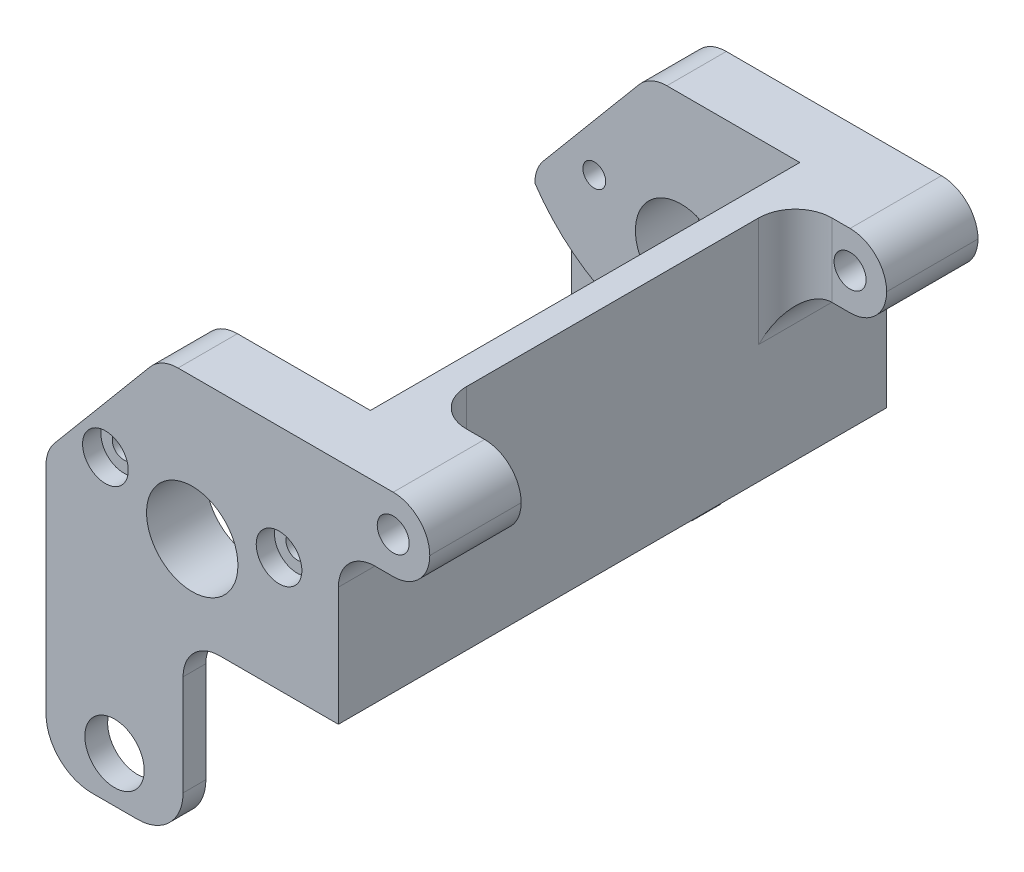
SolidWorks part; units mm, degrees
ref_plane "Front Plane" through (0, 0, 0) normal (0, 0, 1) x (1, 0, 0)
ref_plane "Top Plane" through (0, 0, 0) normal (0, 1, 0) x (1, 0, 0)
ref_plane "Right Plane" through (0, 0, 0) normal (1, 0, 0) x (0, 0, -1)
sketch "Sketch2" plane through (0, 0, 0) normal (0, 0, 1) x (1, 0, 0)
  line L0 (-7.5, 5) -> (-7.5, 30)
  line L1 (-7.5, 30) -> (5.0865, 45)
  line L2 (5.0865, 45) -> (24.5, 45)
  line L3 (24.5, 45) -> (24.5, 20)
  line L4 (24.5, 20) -> (7.5, 20)
  line L5 (7.5, 20) -> (7.5, 5)
  line L6 (-2.5, 0) -> (2.5, 0)
  line L7 (-7.5, 0) -> (7.5, 0) construction
  line L8 (-7.5, 5) -> (7.5, 5) construction
  line L9 (18.0048, 32.5697) -> (-0.9952, 32.5697) construction
  line L10 (8.5048, 32.5697) -> (8.5048, 29.5697) construction
  line L11 (0, 5) -> (8.5048, 29.5697) construction
  circle A5 centre (0, 5) radius 3.25
  circle A6 centre (18.0048, 32.5697) radius 1.25
  circle A7 centre (-0.9952, 32.5697) radius 1.25
  circle A8 centre (8.5048, 29.5697) radius 5
  circle A9 centre (8.5048, 32.5697) radius 12.5 construction
  arc A10 (2.5, 0) -> (7.5, 5) centre (2.5, 5) ccw
  arc A11 (-7.5, 5) -> (-2.5, 0) centre (-2.5, 5) ccw
  dimension "D3" = 6.5
  dimension "D4" = 5
  dimension "D10" = 10
  dimension "D12" = 2.5
  dimension "D14" = 25
  dimension "D15" = 5
  dimension "D1" = 40
  dimension "D2" = 15
  dimension "D5" = 30
  dimension "D6" = 15
  dimension "D7" = 17
  dimension "D8" = 20
  dimension "D9" = 19
  dimension "D11" = 3
  dimension "D13" = 26
extrude "Boss-Extrude1" add sketch "Sketch2" along normal blind 30 and the other way blind 30
sketch "Sketch3" plane through (0, 45, 0) normal (0, 1, 0) x (1, 0, 0)
  line L0 (-7.5, -30) -> (-7.5, 30) construction
  line L1 (-36.5, -27.5) -> (21.5, -27.5)
  line L2 (-36.5, -27.5) -> (-36.5, 27.5)
  line L3 (-36.5, 27.5) -> (21.5, 27.5)
  line L4 (21.5, -27.5) -> (21.5, 27.5)
  line L5 (-36.5, -27.5) -> (21.5, 27.5) construction
  line L6 (-36.5, 27.5) -> (21.5, -27.5) construction
  line L7 (24.5, 30) -> (5.0865, 30) construction
  line L8 (24.5, -30) -> (24.5, 30) construction
  point P0 (-7.5, 0)
  dimension "D1" = 2.5
  dimension "D2" = 3
extrude "Cut-Extrude1" cut sketch "Sketch3" against normal through all
sketch "Sketch4" plane through (24.5, 0, 0) normal (1, 0, 0) x (0, 0, -1)
  line L1 (-30, 45) -> (-20, 45)
  line L2 (-30, 45) -> (-30, 37)
  line L3 (-30, 37) -> (-20, 37)
  line L4 (-20, 45) -> (-20, 37)
  dimension "D1" = 10
  dimension "D2" = 8
extrude "Boss-Extrude2" add sketch "Sketch4" along normal blind 10
fillet "Fillet1" radius 4 2 edges at (34.5, 37, 25) (34.5, 45, 25)
sketch "Sketch5" plane through (0, 0, 20) normal (0, 0, -1) x (-1, 0, 0)
  circle A0 centre (-30.5, 41) radius 1.75
  dimension "D1" = 3.5
extrude "Cut-Extrude2" cut sketch "Sketch5" against normal through all
mirror "Mirror1" about plane through (0, 0, 0) normal (0, 0, 1) of "Cut-Extrude2", "Fillet1", "Boss-Extrude2"
fillet "Fillet2" radius 4 10 edges at (24.5, 41, -20) (24.5, 41, 20) (5.0865, 45, -28.75) (7.5, 20, -28.75) (24.5, 37, -25) (24.5, 37, 25) (7.5, 20, 28.75) (5.0865, 45, 28.75) (-7.5, 30, 28.75) (-7.5, 30, -28.75)
sketch "Sketch6" plane through (0, 0, -27.5) normal (0, 0, 1) x (1, 0, 0)
  line L0 (-0.9952, 32.5697) -> (18.0048, 32.5697) construction
  line L7 (21.5, 45) -> (6.9517, 45)
  line L8 (3.8875, 43.5712) -> (-6.5642, 31.1153)
  line L9 (-7.5, 28.5441) -> (-7.5, 5)
  line L10 (-2.5, 0) -> (2.5, 0)
  line L11 (7.5, 5) -> (7.5, 16)
  line L12 (11.5, 20) -> (21.5, 20)
  line L13 (21.5, 20) -> (21.5, 45)
  line L14 (21.5, 45) -> (6.9517, 45)
  line L15 (3.8875, 43.5712) -> (-6.5642, 31.1153)
  line L19 (11.5, 20) -> (21.5, 20)
  line L20 (21.5, 20) -> (21.5, 45)
  arc A1 (11.5, 20) -> (-7.5, 28.5441) centre (8.8465, 39.497) cw
  circle A2 centre (18.0048, 32.5697) radius 1.25 construction
  circle A3 centre (8.5048, 29.5697) radius 5 construction
  circle A4 centre (-0.9952, 32.5697) radius 1.25 construction
  circle A5 centre (18.0048, 32.5697) radius 1.25
  arc A6 (6.9517, 45) -> (3.8875, 43.5712) centre (6.9517, 41) ccw
  arc A7 (-6.5642, 31.1153) -> (-7.5, 28.5441) centre (-3.5, 28.5441) ccw
  arc A8 (-7.5, 5) -> (-2.5, 0) centre (-2.5, 5) ccw
  arc A9 (2.5, 0) -> (7.5, 5) centre (2.5, 5) ccw
  arc A10 (11.5, 20) -> (7.5, 16) centre (11.5, 16) ccw
  arc A11 (6.9517, 45) -> (3.8875, 43.5712) centre (6.9517, 41) ccw
  arc A12 (-6.5642, 31.1153) -> (-7.5, 28.5441) centre (-3.5, 28.5441) ccw
  circle A16 centre (8.5048, 29.5697) radius 5
  circle A17 centre (-0.9952, 32.5697) radius 1.25
  dimension "D1" = 0
extrude "Boss-Extrude3" add sketch "Sketch6" along normal blind 4
sketch "Sketch7" plane through (0, 0, -30) normal (0, 0, -1) x (-1, 0, 0)
  circle A0 centre (-18.0048, 32.5697) radius 2.5
  circle A1 centre (0.9952, 32.5697) radius 2.5
  dimension "D1" = 5
extrude "Cut-Extrude3" cut sketch "Sketch7" against normal blind 2
mirror "Mirror2" about plane through (0, 0, 0) normal (0, 0, 1) of "Cut-Extrude3", "Boss-Extrude3"
